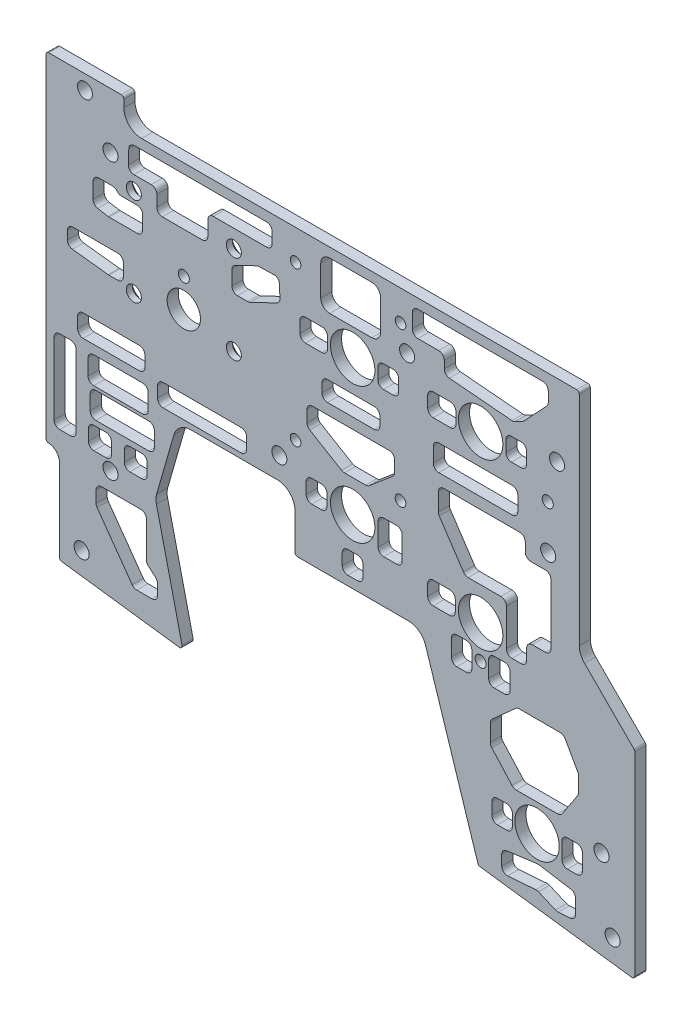
SolidWorks part; units mm, degrees
ref_plane "Front Plane" through (0, 0, 0) normal (0, 0, 1) x (1, 0, 0)
ref_plane "Top Plane" through (0, 0, 0) normal (0, 1, 0) x (1, 0, 0)
ref_plane "Right Plane" through (0, 0, 0) normal (1, 0, 0) x (0, 0, -1)
sketch "Sketch1" plane through (0, 0, 0) normal (0, 0, 1) x (1, 0, 0)
  line L16 (3.81, -91.8845) -> (3.81, -115.4033)
  line L17 (4.4725, -116.1588) -> (38.0231, -120.5758)
  line L18 (38.8645, -119.6465) -> (31.5446, -88.4134)
  line L19 (31.6093, -85.8475) -> (36.5334, -68.7608)
  line L20 (41.4148, -65.0875) -> (66.04, -65.0875)
  line L21 (71.12, -70.1675) -> (71.12, -80.518)
  line L22 (71.882, -81.28) -> (103.6122, -81.28)
  line L23 (108.4484, -84.805) -> (123.4233, -131.3792)
  line L24 (124.0493, -131.9014) -> (167.4135, -137.6104)
  line L25 (168.275, -136.8549) -> (168.275, -81.3036)
  line L26 (168.0518, -80.7647) -> (153.8879, -66.6008)
  line L27 (152.4, -63.0087) -> (152.4, -0.762)
  line L28 (151.638, 0) -> (27.305, 0)
  line L29 (22.225, 5.08) -> (22.225, 7.1755)
  line L30 (21.463, 7.9375) -> (0.762, 7.9375)
  line L31 (0, 7.1755) -> (0, -87.9495)
  line L32 (3.81, -91.8845) -> (3.81, -115.4033)
  line L33 (4.4725, -116.1588) -> (38.0231, -120.5758)
  line L34 (38.8645, -119.6465) -> (31.5446, -88.4134)
  line L35 (31.6093, -85.8475) -> (36.5334, -68.7608)
  line L36 (41.4148, -65.0875) -> (66.04, -65.0875)
  line L37 (71.12, -70.1675) -> (71.12, -80.518)
  line L38 (71.882, -81.28) -> (103.6122, -81.28)
  line L39 (108.4484, -84.805) -> (123.4233, -131.3792)
  line L40 (124.0493, -131.9014) -> (167.4135, -137.6104)
  line L41 (168.275, -136.8549) -> (168.275, -81.3036)
  line L42 (168.0518, -80.7647) -> (153.8879, -66.6008)
  line L43 (152.4, -63.0087) -> (152.4, -0.762)
  line L44 (151.638, 0) -> (27.305, 0)
  line L45 (22.225, 5.08) -> (22.225, 7.1755)
  line L46 (21.463, 7.9375) -> (0.762, 7.9375)
  line L47 (0, 7.1755) -> (0, -87.9495)
  arc A17 (3.81, -91.8845) -> (0.7374, -88.7112) centre (0.635, -91.8845) ccw
  arc A18 (3.81, -115.4033) -> (4.4725, -116.1588) centre (4.572, -115.4033) ccw
  arc A19 (38.0231, -120.5758) -> (38.8645, -119.6465) centre (38.1226, -119.8204) ccw
  arc A20 (31.6093, -85.8475) -> (31.5446, -88.4134) centre (36.4906, -87.2542) ccw
  arc A21 (41.4148, -65.0875) -> (36.5334, -68.7608) centre (41.4148, -70.1675) ccw
  arc A22 (71.12, -70.1675) -> (66.04, -65.0875) centre (66.04, -70.1675) ccw
  arc A23 (71.12, -80.518) -> (71.882, -81.28) centre (71.882, -80.518) ccw
  arc A24 (108.4484, -84.805) -> (103.6122, -81.28) centre (103.6122, -86.36) ccw
  arc A25 (123.4233, -131.3792) -> (124.0493, -131.9014) centre (124.1487, -131.1459) ccw
  arc A26 (167.4135, -137.6104) -> (168.275, -136.8549) centre (167.513, -136.8549) ccw
  arc A27 (168.275, -81.3036) -> (168.0518, -80.7647) centre (167.513, -81.3036) ccw
  arc A28 (152.4, -63.0087) -> (153.8879, -66.6008) centre (157.48, -63.0087) ccw
  arc A29 (152.4, -0.762) -> (151.638, 0) centre (151.638, -0.762) ccw
  arc A30 (22.225, 5.08) -> (27.305, 0) centre (27.305, 5.08) ccw
  arc A31 (22.225, 7.1755) -> (21.463, 7.9375) centre (21.463, 7.1755) ccw
  arc A32 (0.762, 7.9375) -> (0, 7.1755) centre (0.762, 7.1755) ccw
  arc A33 (0, -87.9495) -> (0.7374, -88.7112) centre (0.762, -87.9495) ccw
  arc A34 (3.81, -91.8845) -> (0.7374, -88.7112) centre (0.635, -91.8845) ccw
  arc A35 (3.81, -115.4033) -> (4.4725, -116.1588) centre (4.572, -115.4033) ccw
  arc A36 (38.0231, -120.5758) -> (38.8645, -119.6465) centre (38.1226, -119.8204) ccw
  arc A37 (31.6093, -85.8475) -> (31.5446, -88.4134) centre (36.4906, -87.2542) ccw
  arc A38 (41.4148, -65.0875) -> (36.5334, -68.7608) centre (41.4148, -70.1675) ccw
  arc A39 (71.12, -70.1675) -> (66.04, -65.0875) centre (66.04, -70.1675) ccw
  arc A40 (71.12, -80.518) -> (71.882, -81.28) centre (71.882, -80.518) ccw
  arc A41 (108.4484, -84.805) -> (103.6122, -81.28) centre (103.6122, -86.36) ccw
  arc A42 (123.4233, -131.3792) -> (124.0493, -131.9014) centre (124.1487, -131.1459) ccw
  arc A43 (167.4135, -137.6104) -> (168.275, -136.8549) centre (167.513, -136.8549) ccw
  arc A44 (168.275, -81.3036) -> (168.0518, -80.7647) centre (167.513, -81.3036) ccw
  arc A45 (152.4, -63.0087) -> (153.8879, -66.6008) centre (157.48, -63.0087) ccw
  arc A46 (152.4, -0.762) -> (151.638, 0) centre (151.638, -0.762) ccw
  arc A47 (22.225, 5.08) -> (27.305, 0) centre (27.305, 5.08) ccw
  arc A48 (22.225, 7.1755) -> (21.463, 7.9375) centre (21.463, 7.1755) ccw
  arc A49 (0.762, 7.9375) -> (0, 7.1755) centre (0.762, 7.1755) ccw
  arc A50 (0, -87.9495) -> (0.7374, -88.7112) centre (0.762, -87.9495) ccw
  dimension "D1" = 0
extrude "Boss-Extrude1" add sketch "Sketch1" against normal blind 3.175
hole_wizard "#6 Clearance Hole1" positions "Sketch3" profile "Sketch2" hole size "#6" standard "ANSI Inch" end condition through all
sketch "Sketch3" plane through (0, 0, -3.175) normal (0, 0, -1) x (-1, 0, 0)
  point P0 (-11.1125, 3.81)
  point P3 (-18.415, -7.9375)
  point P6 (-103.1875, -15.24)
  point P9 (-143.51, -44.45)
  point P12 (-158.75, -111.125)
  point P15 (-18.415, -86.741)
  point P18 (-66.675, -58.7375)
  point P21 (-10.16, -110.5028)
  point P25 (-146.05, -20.6375)
  point P28 (-161.925, -130.483)
sketch "Sketch2" plane through (11.1125, 3.81, -3.175) normal (1, 0, 0) x (0, 1, 0)
  line L0 (0, 0) -> (0, 3.175)
  line L1 (0, 3.175) -> (2.1526, 3.175)
  line L2 (2.1526, 3.175) -> (2.1526, 0)
  line L5 (2.1526, 0) -> (0, 0)
  line L11 (0, -6.35) -> (0, 107.95) construction
  dimension "Thru Hole Dia." = 4.3053
  dimension "Thru Hole Depth" = 3.175
sketch "Sketch4" plane through (0, 0, -3.175) normal (0, 0, -1) x (-1, 0, 0)
  circle A0 centre (-140.335, -115.57) radius 6.35
  circle A1 centre (-124.206, -71.4375) radius 6.35
  circle A2 centre (-87.63, -62.992) radius 6.35
  circle A3 centre (-87.63, -24.13) radius 6.35
  circle A4 centre (-124.206, -24.13) radius 6.35
  circle A5 centre (-124.206, -80.9625) radius 1.5875
  circle A6 centre (-39.37, -36.322) radius 4.7625
  dimension "D1" = 12.7
  dimension "D2" = 3.175
  dimension "D4" = 9.525
  dimension "D3" = 9.525
extrude "Cut-Extrude1" cut sketch "Sketch4" against normal through all
hole_wizard "CSK for #6 Flat Head Machine Screw (100)1" positions "Sketch6" profile "Sketch5" countersink size "#6" standard "ANSI Inch" end condition through all
sketch "Sketch6" plane through (0, 0, -3.175) normal (0, 0, -1) x (-1, 0, 0)
  point P0 (-53.6575, -14.097)
  point P2 (-25.0825, -14.097)
  point P4 (-25.0825, -39.497)
  point P6 (-53.6575, -39.497)
sketch "Sketch5" plane through (53.6575, -14.097, -3.175) normal (1, 0, 0) x (0, 1, 0)
  line L0 (0, 0) -> (0, 3.175)
  line L1 (0, 3.175) -> (2.1526, 3.175)
  line L2 (2.1526, 3.175) -> (2.1526, 1.4209)
  line L3 (2.1526, 1.4209) -> (3.846, 0)
  line L5 (3.846, 0) -> (0, 0)
  line L6 (-2.1526, 1.4209) -> (-3.846, 0) construction
  line L11 (0, -6.35) -> (0, 107.95) construction
  dimension "Thru Hole Dia." = 4.3053
  dimension "Thru Hole Depth" = 3.175
  dimension "Near C'Sink Dia." = 7.692
  dimension "Near C'Sink Angle" = 100
hole_wizard "#0 Clearance Hole1" positions "Sketch7" profile "Sketch8" hole size "#0" standard "ANSI Inch" end condition through all
sketch "Sketch7" plane through (0, 0, -9.525) normal (0, 0, -1) x (-1, 0, 0)
  point P0 (-39.37, -28.067)
sketch "Sketch8" plane through (39.37, -28.067, -9.525) normal (1, 0, 0) x (0, 1, 0)
  line L0 (0, 0) -> (0, 9.525)
  line L1 (0, 9.525) -> (0.9271, 9.525)
  line L2 (0.9271, 9.525) -> (0.9271, 0)
  line L3 (0.9271, 0) -> (0, 0)
  line L4 (0, -6.35) -> (0, 107.95) construction
  dimension "Thru Hole Dia." = 1.8542
  dimension "Thru Hole Depth" = 9.525
hole_wizard "1/8 (0.125) Diameter Hole1" positions "Sketch9" profile "Sketch10" hole size "1/8" standard "ANSI Inch" end condition through all
sketch "Sketch9" plane through (0, 0, 0) normal (0, 0, 1) x (1, 0, 0)
  point P0 (39.37, -28.067)
sketch "Sketch10" plane through (39.37, -28.067, 0) normal (1, 0, 0) x (0, -1, 0)
  line L0 (0, 0) -> (0, 3.175)
  line L1 (0, 3.175) -> (1.5875, 3.175)
  line L2 (1.5875, 3.175) -> (1.5875, 0)
  line L5 (1.5875, 0) -> (0, 0)
  line L11 (0, -6.35) -> (0, 107.95) construction
  dimension "Thru Hole Dia." = 3.175
  dimension "Thru Hole Depth" = 3.175
sketch "Sketch17" plane through (0, 0, 0) normal (0, 0, -1) x (-1, 0, 0)
  line L0 (-141.9544, -2.7948) -> (-106.2662, -2.7948)
  line L1 (-104.6787, -4.3823) -> (-104.6787, -8.4606)
  line L2 (-106.2662, -10.0481) -> (-112.2209, -10.0481)
  line L3 (-113.8084, -11.6356) -> (-113.8084, -13.7762)
  line L4 (-115.259, -15.3578) -> (-133.159, -16.9076)
  line L5 (-134.0131, -16.7423) -> (-136.0874, -15.6921)
  line L6 (-136.5298, -15.36) -> (-143.114, -8.3185)
  line L7 (-143.5419, -7.2342) -> (-143.5419, -4.3823)
  line L8 (-93.0669, -2.7076) -> (-81.0441, -2.7076)
  line L9 (-78.5041, -5.2476) -> (-78.5041, -13.8956)
  line L10 (-81.0441, -16.4356) -> (-93.0669, -16.4356)
  line L11 (-95.6069, -13.8956) -> (-95.6069, -5.2476)
  line L12 (-72.5612, -22.437) -> (-72.5612, -25.637)
  line L13 (-74.1487, -27.2245) -> (-78.851, -27.2245)
  line L14 (-80.4385, -25.637) -> (-80.4385, -22.437)
  line L15 (-74.1487, -20.8495) -> (-78.851, -20.8495)
  line L16 (-99.2018, -21.1963) -> (-96.4213, -21.1963)
  line L17 (-94.8338, -22.7838) -> (-94.8338, -25.9818)
  line L18 (-96.4213, -27.5693) -> (-99.2018, -27.5693)
  line L19 (-100.7893, -25.9818) -> (-100.7893, -22.7838)
  line L20 (-109.0792, -22.6549) -> (-109.0792, -25.8549)
  line L21 (-110.6667, -27.4424) -> (-115.5536, -27.4424)
  line L22 (-117.1411, -25.8549) -> (-117.1411, -22.6549)
  line L23 (-110.6667, -21.0674) -> (-115.5536, -21.0674)
  line L24 (-135.7738, -20.8814) -> (-132.9933, -20.8814)
  line L25 (-131.4058, -22.4689) -> (-131.4058, -25.667)
  line L26 (-132.9933, -27.2545) -> (-135.7738, -27.2545)
  line L27 (-137.3613, -25.667) -> (-137.3613, -22.4689)
  line L28 (-93.8189, -33.0853) -> (-80.4385, -33.0853)
  line L29 (-78.851, -34.6728) -> (-78.851, -37.1954)
  line L30 (-80.4385, -38.7829) -> (-93.8189, -38.7829)
  line L31 (-95.4064, -34.6728) -> (-95.4064, -37.1954)
  line L32 (-133.2346, -32.9063) -> (-112.2542, -32.9063)
  line L33 (-110.6667, -34.4938) -> (-110.6667, -38.6545)
  line L34 (-112.2542, -40.242) -> (-133.2346, -40.242)
  line L35 (-134.8221, -38.6545) -> (-134.8221, -34.4938)
  line L36 (-98.0498, -41.8469) -> (-76.1717, -41.8469)
  line L37 (-74.5842, -43.4344) -> (-74.5842, -46.7771)
  line L38 (-75.3596, -48.1412) -> (-84.4657, -53.5626)
  line L39 (-85.2778, -53.7861) -> (-91.3474, -53.7861)
  line L40 (-92.3756, -53.4081) -> (-99.0779, -47.711)
  line L41 (-99.6373, -46.5014) -> (-99.6373, -43.4344)
  line L42 (-135.3789, -43.4344) -> (-113.699, -43.4344)
  line L43 (-112.1115, -45.0219) -> (-112.1115, -50.0429)
  line L44 (-112.3789, -50.9245) -> (-119.3229, -61.3222)
  line L45 (-120.6431, -62.0281) -> (-129.9871, -62.0281)
  line L47 (-136.9664, -47.5212) -> (-136.9664, -45.0219)
  line L48 (-55.7285, -57.3176) -> (-33.4587, -57.3176)
  line L49 (-31.8712, -58.9051) -> (-31.8712, -62.02)
  line L50 (-33.4587, -63.6075) -> (-55.7285, -63.6075)
  line L51 (-57.316, -62.02) -> (-57.316, -58.9051)
  line L52 (-78.7021, -59.8174) -> (-75.9216, -59.8174)
  line L53 (-74.3341, -61.4049) -> (-74.3341, -64.603)
  line L54 (-75.9216, -66.1905) -> (-78.7021, -66.1905)
  line L55 (-80.2896, -64.603) -> (-80.2896, -61.4049)
  line L56 (-89.0189, -72.2548) -> (-86.2384, -72.2548)
  line L57 (-84.6509, -73.8423) -> (-84.6509, -77.0403)
  line L58 (-86.2384, -78.6278) -> (-89.0189, -78.6278)
  line L59 (-90.6064, -77.0403) -> (-90.6064, -73.8423)
  line L60 (-109.0756, -69.248) -> (-109.0756, -72.448)
  line L61 (-110.6631, -74.0355) -> (-115.3654, -74.0355)
  line L62 (-116.9529, -72.448) -> (-116.9529, -69.248)
  line L63 (-110.6631, -67.6605) -> (-115.3654, -67.6605)
  line L64 (-148.3701, -88.0766) -> (-151.9572, -94.4661)
  line L65 (-152.1698, -95.2794) -> (-152.1698, -99.4916)
  line L66 (-151.8961, -100.4052) -> (-147.5598, -106.9917)
  line L67 (-138.5539, -49.1087) -> (-142.7058, -49.1087)
  line L68 (-146.1721, -107.7395) -> (-134.3926, -107.7395)
  line L69 (-144.2933, -50.6962) -> (-144.2933, -67.8867)
  line L70 (-133.1575, -107.1893) -> (-127.3956, -100.785)
  line L71 (-126.9693, -99.6738) -> (-126.9693, -94.8668)
  line L72 (-127.5195, -93.6317) -> (-134.1629, -87.6548)
  line L73 (-135.2742, -87.2285) -> (-146.9213, -87.2285)
  line L74 (-137.3613, -71.0617) -> (-137.3613, -74.1715)
  line L75 (-135.7738, -75.759) -> (-133.1621, -75.759)
  line L76 (-131.5746, -74.1715) -> (-131.5746, -63.6156)
  line L78 (-132.6264, -79.3569) -> (-132.6264, -84.055)
  line L79 (-131.0389, -85.6425) -> (-128.0874, -85.6425)
  line L80 (-126.4999, -84.055) -> (-126.4999, -79.3653)
  line L81 (-128.0829, -77.7778) -> (-131.0344, -77.7694)
  line L82 (-121.6938, -79.414) -> (-121.6938, -84.1113)
  line L83 (-120.1063, -85.6988) -> (-117.4258, -85.6988)
  line L84 (-115.8383, -84.1113) -> (-115.8383, -79.4216)
  line L85 (-117.4212, -77.8341) -> (-120.1018, -77.8265)
  line L86 (-101.7978, -60.9375) -> (-101.7978, -67.3473)
  line L87 (-100.2103, -68.9348) -> (-96.4976, -68.9348)
  line L88 (-94.9101, -67.3473) -> (-94.9101, -60.9481)
  line L89 (-96.4931, -59.3606) -> (-100.2058, -59.35)
  line L90 (-153.2801, -113.8454) -> (-153.2801, -118.4115)
  line L91 (-151.6926, -119.999) -> (-149.0121, -119.999)
  line L92 (-147.4246, -118.4115) -> (-147.4246, -113.853)
  line L93 (-149.0076, -112.2655) -> (-151.6881, -112.2579)
  line L94 (-133.2696, -114.0603) -> (-133.2696, -117.4522)
  line L95 (-131.6821, -119.0397) -> (-129.0016, -119.0397)
  line L96 (-127.4141, -117.4522) -> (-127.4141, -114.0679)
  line L97 (-128.997, -112.4804) -> (-131.6776, -112.4728)
  line L98 (-150.0084, -124.4751) -> (-140.8902, -122.9925)
  line L99 (-140.4256, -122.9858) -> (-131.6139, -124.1607)
  line L100 (-130.2362, -125.7343) -> (-130.2362, -128.6297)
  line L101 (-131.9392, -130.213) -> (-139.9781, -129.6268)
  line L102 (-140.7126, -129.7482) -> (-145.6471, -131.838)
  line L103 (-146.3817, -131.9595) -> (-149.8691, -131.7052)
  line L104 (-151.3411, -130.1219) -> (-151.3411, -126.042)
  line L105 (-63.0404, -2.7948) -> (-25.2277, -2.7948)
  line L106 (-23.641, -4.3315) -> (-23.5105, -8.4099)
  line L107 (-25.0972, -10.0481) -> (-30.0725, -10.0481)
  line L108 (-31.66, -11.6356) -> (-31.66, -14.8481)
  line L109 (-33.2475, -16.4356) -> (-44.6401, -16.4356)
  line L110 (-46.2276, -14.8481) -> (-46.2276, -10.6224)
  line L111 (-47.8151, -9.0349) -> (-63.0404, -9.0349)
  line L112 (-64.6279, -7.4474) -> (-64.6279, -4.3823)
  line L113 (-14.7591, -23.5708) -> (-17.7234, -24.0903)
  line L114 (-17.9974, -24.1142) -> (-26.0381, -24.1142)
  line L115 (-27.6256, -22.5267) -> (-27.6256, -18.7366)
  line L116 (-26.0381, -17.1491) -> (-21.5632, -17.1491)
  line L117 (-20.4504, -16.6939) -> (-20.1204, -16.3695)
  line L118 (-19.0076, -15.9142) -> (-15.0331, -15.9142)
  line L119 (-13.4456, -17.5017) -> (-13.4456, -22.0071)
  line L120 (-7.6875, -31.7843) -> (-20.4927, -31.7843)
  line L121 (-22.0802, -33.3718) -> (-22.0802, -36.9105)
  line L122 (-20.4927, -38.498) -> (-17.9504, -38.498)
  line L123 (-17.7686, -38.4875) -> (-7.5058, -37.3048)
  line L124 (-6.1, -35.7277) -> (-6.1, -33.3718)
  line L125 (-54.0177, -18.0353) -> (-60.157, -15.0963)
  line L126 (-60.7931, -14.9415) -> (-65.0805, -14.8081)
  line L127 (-66.7166, -16.3454) -> (-66.8282, -19.9294)
  line L128 (-65.9269, -21.4107) -> (-58.3022, -25.0607)
  line L129 (-57.6167, -25.2163) -> (-54.7032, -25.2163)
  line L130 (-53.1157, -23.6288) -> (-53.1157, -19.4672)
  line L131 (-24.6224, -111.8142) -> (-14.5986, -97.7476)
  line L132 (-14.304, -96.8263) -> (-14.304, -93.5113)
  line L133 (-2.2976, -61.6269) -> (-2.2976, -82.1859)
  line L134 (-3.8851, -83.7734) -> (-6.9926, -83.7734)
  line L135 (-8.5801, -82.1859) -> (-8.5801, -61.6269)
  line L136 (-6.9926, -60.0394) -> (-3.8851, -60.0394)
  line L137 (-15.8915, -91.9238) -> (-27.0858, -91.9238)
  line L138 (-28.6733, -93.5113) -> (-28.6733, -103.656)
  line L139 (-29.2117, -104.8474) -> (-31.3328, -106.7152)
  line L140 (-31.8712, -107.9067) -> (-31.8712, -110.8929)
  line L141 (-30.2837, -112.4804) -> (-25.9153, -112.4804)
  line L142 (-26.655, -51.5392) -> (-10.6039, -51.5392)
  line L143 (-9.0164, -53.1267) -> (-9.0164, -56.2416)
  line L144 (-10.6039, -57.8291) -> (-26.655, -57.8291)
  line L145 (-28.2425, -56.2416) -> (-28.2425, -53.1267)
  line L146 (-27.6052, -60.385) -> (-13.5866, -60.385)
  line L147 (-11.9991, -61.9725) -> (-11.9991, -66.4544)
  line L148 (-13.5866, -68.0419) -> (-27.6052, -68.0419)
  line L149 (-29.1927, -66.4544) -> (-29.1927, -61.9725)
  line L150 (-29.347, -68.9032) -> (-14.2014, -68.9032)
  line L151 (-12.6139, -70.4907) -> (-12.6139, -74.7412)
  line L152 (-14.2014, -76.3287) -> (-29.347, -76.3287)
  line L153 (-30.9345, -74.7412) -> (-30.9345, -70.4907)
  line L154 (-27.3287, -77.9076) -> (-23.9481, -77.9076)
  line L155 (-22.3606, -79.4951) -> (-22.3606, -82.61)
  line L156 (-23.9481, -84.1975) -> (-27.3287, -84.1975)
  line L157 (-28.9162, -82.61) -> (-28.9162, -79.4951)
  line L158 (-17.1192, -77.821) -> (-13.667, -77.821)
  line L159 (-12.0795, -79.4085) -> (-12.0795, -82.5234)
  line L160 (-13.667, -84.1109) -> (-17.1192, -84.1109)
  line L161 (-18.7067, -82.5234) -> (-18.7067, -79.4085)
  line L162 (-142.7058, -69.4742) -> (-138.9488, -69.4742)
  arc A0 (-106.2662, -2.7948) -> (-104.6787, -4.3823) centre (-106.2662, -4.3823) cw
  arc A1 (-104.6787, -8.4606) -> (-106.2662, -10.0481) centre (-106.2662, -8.4606) cw
  arc A2 (-112.2209, -10.0481) -> (-113.8084, -11.6356) centre (-112.2209, -11.6356) ccw
  arc A3 (-113.8084, -13.7762) -> (-115.259, -15.3578) centre (-115.3959, -13.7762) cw
  arc A4 (-133.159, -16.9076) -> (-134.0131, -16.7423) centre (-133.296, -15.326) cw
  arc A5 (-136.0874, -15.6921) -> (-136.5298, -15.36) centre (-135.3703, -14.2758) cw
  arc A6 (-143.114, -8.3185) -> (-143.5419, -7.2342) centre (-141.9544, -7.2342) cw
  arc A7 (-141.9544, -2.7948) -> (-143.5419, -4.3823) centre (-141.9544, -4.3823) ccw
  arc A8 (-81.0441, -2.7076) -> (-78.5041, -5.2476) centre (-81.0441, -5.2476) cw
  arc A9 (-78.5041, -13.8956) -> (-81.0441, -16.4356) centre (-81.0441, -13.8956) cw
  arc A10 (-93.0669, -16.4356) -> (-95.6069, -13.8956) centre (-93.0669, -13.8956) cw
  arc A11 (-93.0669, -2.7076) -> (-95.6069, -5.2476) centre (-93.0669, -5.2476) ccw
  arc A12 (-72.5612, -22.437) -> (-74.1487, -20.8495) centre (-74.1487, -22.437) ccw
  arc A13 (-72.5612, -25.637) -> (-74.1487, -27.2245) centre (-74.1487, -25.637) cw
  arc A14 (-78.851, -27.2245) -> (-80.4385, -25.637) centre (-78.851, -25.637) cw
  arc A15 (-80.4385, -22.437) -> (-78.851, -20.8495) centre (-78.851, -22.437) cw
  arc A16 (-96.4213, -21.1963) -> (-94.8338, -22.7838) centre (-96.4213, -22.7838) cw
  arc A17 (-94.8338, -25.9818) -> (-96.4213, -27.5693) centre (-96.4213, -25.9818) cw
  arc A18 (-99.2018, -27.5693) -> (-100.7893, -25.9818) centre (-99.2018, -25.9818) cw
  arc A19 (-99.2018, -21.1963) -> (-100.7893, -22.7838) centre (-99.2018, -22.7838) ccw
  arc A20 (-109.0792, -22.6549) -> (-110.6667, -21.0674) centre (-110.6667, -22.6549) ccw
  arc A21 (-109.0792, -25.8549) -> (-110.6667, -27.4424) centre (-110.6667, -25.8549) cw
  arc A22 (-115.5536, -27.4424) -> (-117.1411, -25.8549) centre (-115.5536, -25.8549) cw
  arc A23 (-117.1411, -22.6549) -> (-115.5536, -21.0674) centre (-115.5536, -22.6549) cw
  arc A24 (-132.9933, -20.8814) -> (-131.4058, -22.4689) centre (-132.9933, -22.4689) cw
  arc A25 (-131.4058, -25.667) -> (-132.9933, -27.2545) centre (-132.9933, -25.667) cw
  arc A26 (-135.7738, -27.2545) -> (-137.3613, -25.667) centre (-135.7738, -25.667) cw
  arc A27 (-135.7738, -20.8814) -> (-137.3613, -22.4689) centre (-135.7738, -22.4689) ccw
  arc A28 (-80.4385, -33.0853) -> (-78.851, -34.6728) centre (-80.4385, -34.6728) cw
  arc A29 (-78.851, -37.1954) -> (-80.4385, -38.7829) centre (-80.4385, -37.1954) cw
  arc A30 (-93.8189, -38.7829) -> (-95.4064, -37.1954) centre (-93.8189, -37.1954) cw
  arc A31 (-93.8189, -33.0853) -> (-95.4064, -34.6728) centre (-93.8189, -34.6728) ccw
  arc A32 (-112.2542, -32.9063) -> (-110.6667, -34.4938) centre (-112.2542, -34.4938) cw
  arc A33 (-110.6667, -38.6545) -> (-112.2542, -40.242) centre (-112.2542, -38.6545) cw
  arc A34 (-133.2346, -40.242) -> (-134.8221, -38.6545) centre (-133.2346, -38.6545) cw
  arc A35 (-133.2346, -32.9063) -> (-134.8221, -34.4938) centre (-133.2346, -34.4938) ccw
  arc A36 (-91.3474, -53.7861) -> (-92.3756, -53.4081) centre (-91.3474, -52.1986) cw
  arc A37 (-84.4657, -53.5626) -> (-85.2778, -53.7861) centre (-85.2778, -52.1986) cw
  arc A38 (-74.5842, -46.7771) -> (-75.3596, -48.1412) centre (-76.1717, -46.7771) cw
  arc A39 (-76.1717, -41.8469) -> (-74.5842, -43.4344) centre (-76.1717, -43.4344) cw
  arc A40 (-98.0498, -41.8469) -> (-99.6373, -43.4344) centre (-98.0498, -43.4344) ccw
  arc A41 (-99.0779, -47.711) -> (-99.6373, -46.5014) centre (-98.0498, -46.5014) cw
  arc A42 (-113.699, -43.4344) -> (-112.1115, -45.0219) centre (-113.699, -45.0219) cw
  arc A43 (-112.1115, -50.0429) -> (-112.3789, -50.9245) centre (-113.699, -50.0429) cw
  arc A44 (-119.3229, -61.3222) -> (-120.6431, -62.0281) centre (-120.6431, -60.4406) cw
  arc A47 (-135.3789, -43.4344) -> (-136.9664, -45.0219) centre (-135.3789, -45.0219) ccw
  arc A48 (-33.4587, -57.3176) -> (-31.8712, -58.9051) centre (-33.4587, -58.9051) cw
  arc A49 (-31.8712, -62.02) -> (-33.4587, -63.6075) centre (-33.4587, -62.02) cw
  arc A50 (-55.7285, -63.6075) -> (-57.316, -62.02) centre (-55.7285, -62.02) cw
  arc A51 (-55.7285, -57.3176) -> (-57.316, -58.9051) centre (-55.7285, -58.9051) ccw
  arc A52 (-75.9216, -59.8174) -> (-74.3341, -61.4049) centre (-75.9216, -61.4049) cw
  arc A53 (-74.3341, -64.603) -> (-75.9216, -66.1905) centre (-75.9216, -64.603) cw
  arc A54 (-78.7021, -66.1905) -> (-80.2896, -64.603) centre (-78.7021, -64.603) cw
  arc A55 (-78.7021, -59.8174) -> (-80.2896, -61.4049) centre (-78.7021, -61.4049) ccw
  arc A56 (-86.2384, -72.2548) -> (-84.6509, -73.8423) centre (-86.2384, -73.8423) cw
  arc A57 (-84.6509, -77.0403) -> (-86.2384, -78.6278) centre (-86.2384, -77.0403) cw
  arc A58 (-89.0189, -78.6278) -> (-90.6064, -77.0403) centre (-89.0189, -77.0403) cw
  arc A59 (-89.0189, -72.2548) -> (-90.6064, -73.8423) centre (-89.0189, -73.8423) ccw
  arc A60 (-109.0756, -69.248) -> (-110.6631, -67.6605) centre (-110.6631, -69.248) ccw
  arc A61 (-109.0756, -72.448) -> (-110.6631, -74.0355) centre (-110.6631, -72.448) cw
  arc A62 (-115.3654, -74.0355) -> (-116.9529, -72.448) centre (-115.3654, -72.448) cw
  arc A63 (-116.9529, -69.248) -> (-115.3654, -67.6605) centre (-115.3654, -69.248) cw
  arc A64 (-134.1629, -87.6548) -> (-135.2742, -87.2285) centre (-135.2742, -88.8899) ccw
  arc A65 (-126.9693, -94.8668) -> (-127.5195, -93.6317) centre (-128.6308, -94.8668) ccw
  arc A66 (-127.3956, -100.785) -> (-126.9693, -99.6738) centre (-128.6308, -99.6738) ccw
  arc A67 (-134.3926, -107.7395) -> (-133.1575, -107.1893) centre (-134.3926, -106.0781) ccw
  arc A68 (-147.5598, -106.9917) -> (-146.1721, -107.7395) centre (-146.1721, -106.0781) ccw
  arc A69 (-152.1698, -99.4916) -> (-151.8961, -100.4052) centre (-150.5084, -99.4916) ccw
  arc A70 (-151.9572, -94.4661) -> (-152.1698, -95.2794) centre (-150.5084, -95.2794) ccw
  arc A71 (-148.3701, -88.0766) -> (-146.9213, -87.2285) centre (-146.9213, -88.8899) cw
  arc A74 (-133.1621, -75.759) -> (-131.5746, -74.1715) centre (-133.1621, -74.1715) ccw
  arc A75 (-137.3613, -74.1715) -> (-135.7738, -75.759) centre (-135.7738, -74.1715) ccw
  arc A76 (-132.6264, -79.3569) -> (-131.0344, -77.7694) centre (-131.0389, -79.3569) cw
  arc A77 (-126.4999, -79.3653) -> (-128.0829, -77.7778) centre (-128.0874, -79.3653) ccw
  arc A78 (-128.0874, -85.6425) -> (-126.4999, -84.055) centre (-128.0874, -84.055) ccw
  arc A79 (-132.6264, -84.055) -> (-131.0389, -85.6425) centre (-131.0389, -84.055) ccw
  arc A80 (-121.6938, -79.414) -> (-120.1018, -77.8265) centre (-120.1063, -79.414) cw
  arc A81 (-115.8383, -79.4216) -> (-117.4212, -77.8341) centre (-117.4258, -79.4216) ccw
  arc A82 (-117.4258, -85.6988) -> (-115.8383, -84.1113) centre (-117.4258, -84.1113) ccw
  arc A83 (-121.6938, -84.1113) -> (-120.1063, -85.6988) centre (-120.1063, -84.1113) ccw
  arc A84 (-101.7978, -60.9375) -> (-100.2058, -59.35) centre (-100.2103, -60.9375) cw
  arc A85 (-94.9101, -60.9481) -> (-96.4931, -59.3606) centre (-96.4976, -60.9481) ccw
  arc A86 (-96.4976, -68.9348) -> (-94.9101, -67.3473) centre (-96.4976, -67.3473) ccw
  arc A87 (-101.7978, -67.3473) -> (-100.2103, -68.9348) centre (-100.2103, -67.3473) ccw
  arc A88 (-153.2801, -113.8454) -> (-151.6881, -112.2579) centre (-151.6926, -113.8454) cw
  arc A89 (-147.4246, -113.853) -> (-149.0076, -112.2655) centre (-149.0121, -113.853) ccw
  arc A90 (-149.0121, -119.999) -> (-147.4246, -118.4115) centre (-149.0121, -118.4115) ccw
  arc A91 (-153.2801, -118.4115) -> (-151.6926, -119.999) centre (-151.6926, -118.4115) ccw
  arc A92 (-133.2696, -114.0603) -> (-131.6776, -112.4728) centre (-131.6821, -114.0603) cw
  arc A93 (-127.4141, -114.0679) -> (-128.997, -112.4804) centre (-129.0016, -114.0679) ccw
  arc A94 (-129.0016, -119.0397) -> (-127.4141, -117.4522) centre (-129.0016, -117.4522) ccw
  arc A95 (-133.2696, -117.4522) -> (-131.6821, -119.0397) centre (-131.6821, -117.4522) ccw
  arc A96 (-140.8902, -122.9925) -> (-140.4256, -122.9858) centre (-140.6354, -124.5594) cw
  arc A97 (-131.6139, -124.1607) -> (-130.2362, -125.7343) centre (-131.8237, -125.7343) cw
  arc A98 (-130.2362, -128.6297) -> (-131.9392, -130.213) centre (-131.8237, -128.6297) cw
  arc A99 (-139.9781, -129.6268) -> (-140.7126, -129.7482) centre (-140.0935, -131.2101) ccw
  arc A100 (-145.6471, -131.838) -> (-146.3817, -131.9595) centre (-146.2662, -130.3762) cw
  arc A101 (-149.8691, -131.7052) -> (-151.3411, -130.1219) centre (-149.7536, -130.1219) cw
  arc A102 (-150.0084, -124.4751) -> (-151.3411, -126.042) centre (-149.7536, -126.042) ccw
  arc A103 (-63.0404, -2.7948) -> (-64.6279, -4.3823) centre (-63.0404, -4.3823) ccw
  arc A104 (-25.2277, -2.7948) -> (-23.641, -4.3315) centre (-25.2277, -4.3823) cw
  arc A105 (-23.5105, -8.4099) -> (-25.0972, -10.0481) centre (-25.0972, -8.4606) cw
  arc A106 (-30.0725, -10.0481) -> (-31.66, -11.6356) centre (-30.0725, -11.6356) ccw
  arc A107 (-31.66, -14.8481) -> (-33.2475, -16.4356) centre (-33.2475, -14.8481) cw
  arc A108 (-44.6401, -16.4356) -> (-46.2276, -14.8481) centre (-44.6401, -14.8481) cw
  arc A109 (-46.2276, -10.6224) -> (-47.8151, -9.0349) centre (-47.8151, -10.6224) ccw
  arc A110 (-63.0404, -9.0349) -> (-64.6279, -7.4474) centre (-63.0404, -7.4474) cw
  arc A111 (-23.9481, -77.9076) -> (-22.3606, -79.4951) centre (-23.9481, -79.4951) cw
  arc A112 (-21.5632, -17.1491) -> (-20.4504, -16.6939) centre (-21.5632, -15.5616) ccw
  arc A113 (-20.1204, -16.3695) -> (-19.0076, -15.9142) centre (-19.0076, -17.5017) cw
  arc A114 (-15.0331, -15.9142) -> (-13.4456, -17.5017) centre (-15.0331, -17.5017) cw
  arc A115 (-14.7591, -23.5708) -> (-13.4456, -22.0071) centre (-15.0331, -22.0071) ccw
  arc A116 (-17.7234, -24.0903) -> (-17.9974, -24.1142) centre (-17.9974, -22.5267) cw
  arc A117 (-26.0381, -24.1142) -> (-27.6256, -22.5267) centre (-26.0381, -22.5267) cw
  arc A118 (-27.6256, -18.7366) -> (-26.0381, -17.1491) centre (-26.0381, -18.7366) cw
  arc A119 (-20.4927, -31.7843) -> (-22.0802, -33.3718) centre (-20.4927, -33.3718) ccw
  arc A120 (-22.0802, -36.9105) -> (-20.4927, -38.498) centre (-20.4927, -36.9105) ccw
  arc A121 (-17.9504, -38.498) -> (-17.7686, -38.4875) centre (-17.9504, -36.9105) ccw
  arc A122 (-7.5058, -37.3048) -> (-6.1, -35.7277) centre (-7.6875, -35.7277) ccw
  arc A123 (-7.6875, -31.7843) -> (-6.1, -33.3718) centre (-7.6875, -33.3718) cw
  arc A124 (-58.3022, -25.0607) -> (-57.6167, -25.2163) centre (-57.6167, -23.6288) ccw
  arc A125 (-54.7032, -25.2163) -> (-53.1157, -23.6288) centre (-54.7032, -23.6288) ccw
  arc A126 (-54.0177, -18.0353) -> (-53.1157, -19.4672) centre (-54.7032, -19.4672) cw
  arc A127 (-60.157, -15.0963) -> (-60.7931, -14.9415) centre (-60.8425, -16.5282) ccw
  arc A128 (-65.0805, -14.8081) -> (-66.7166, -16.3454) centre (-65.1299, -16.3948) ccw
  arc A129 (-66.8282, -19.9294) -> (-65.9269, -21.4107) centre (-65.2414, -19.9788) ccw
  arc A130 (-6.9926, -83.7734) -> (-8.5801, -82.1859) centre (-6.9926, -82.1859) cw
  arc A131 (-2.2976, -82.1859) -> (-3.8851, -83.7734) centre (-3.8851, -82.1859) cw
  arc A132 (-3.8851, -60.0394) -> (-2.2976, -61.6269) centre (-3.8851, -61.6269) cw
  arc A133 (-8.5801, -61.6269) -> (-6.9926, -60.0394) centre (-6.9926, -61.6269) cw
  arc A134 (-14.304, -93.5113) -> (-15.8915, -91.9238) centre (-15.8915, -93.5113) ccw
  arc A135 (-14.5986, -97.7476) -> (-14.304, -96.8263) centre (-15.8915, -96.8263) ccw
  arc A136 (-24.6224, -111.8142) -> (-25.9153, -112.4804) centre (-25.9153, -110.8929) cw
  arc A137 (-31.8712, -110.8929) -> (-30.2837, -112.4804) centre (-30.2837, -110.8929) ccw
  arc A138 (-31.3328, -106.7152) -> (-31.8712, -107.9067) centre (-30.2837, -107.9067) ccw
  arc A139 (-28.6733, -103.656) -> (-29.2117, -104.8474) centre (-30.2608, -103.656) cw
  arc A140 (-27.0858, -91.9238) -> (-28.6733, -93.5113) centre (-27.0858, -93.5113) ccw
  arc A141 (-10.6039, -51.5392) -> (-9.0164, -53.1267) centre (-10.6039, -53.1267) cw
  arc A142 (-9.0164, -56.2416) -> (-10.6039, -57.8291) centre (-10.6039, -56.2416) cw
  arc A143 (-26.655, -57.8291) -> (-28.2425, -56.2416) centre (-26.655, -56.2416) cw
  arc A144 (-26.655, -51.5392) -> (-28.2425, -53.1267) centre (-26.655, -53.1267) ccw
  arc A145 (-13.5866, -60.385) -> (-11.9991, -61.9725) centre (-13.5866, -61.9725) cw
  arc A146 (-11.9991, -66.4544) -> (-13.5866, -68.0419) centre (-13.5866, -66.4544) cw
  arc A147 (-27.6052, -68.0419) -> (-29.1927, -66.4544) centre (-27.6052, -66.4544) cw
  arc A148 (-27.6052, -60.385) -> (-29.1927, -61.9725) centre (-27.6052, -61.9725) ccw
  arc A149 (-14.2014, -68.9032) -> (-12.6139, -70.4907) centre (-14.2014, -70.4907) cw
  arc A150 (-12.6139, -74.7412) -> (-14.2014, -76.3287) centre (-14.2014, -74.7412) cw
  arc A151 (-29.347, -76.3287) -> (-30.9345, -74.7412) centre (-29.347, -74.7412) cw
  arc A152 (-29.347, -68.9032) -> (-30.9345, -70.4907) centre (-29.347, -70.4907) ccw
  arc A153 (-22.3606, -82.61) -> (-23.9481, -84.1975) centre (-23.9481, -82.61) cw
  arc A154 (-27.3287, -84.1975) -> (-28.9162, -82.61) centre (-27.3287, -82.61) cw
  arc A155 (-27.3287, -77.9076) -> (-28.9162, -79.4951) centre (-27.3287, -79.4951) ccw
  arc A156 (-13.667, -77.821) -> (-12.0795, -79.4085) centre (-13.667, -79.4085) cw
  arc A157 (-12.0795, -82.5234) -> (-13.667, -84.1109) centre (-13.667, -82.5234) cw
  arc A158 (-17.1192, -84.1109) -> (-18.7067, -82.5234) centre (-17.1192, -82.5234) cw
  arc A159 (-17.1192, -77.821) -> (-18.7067, -79.4085) centre (-17.1192, -79.4085) ccw
  circle A160 centre (-143.3865, -31.863) radius 1.5875
  arc A161 (-136.9664, -47.5212) -> (-138.5539, -49.1087) centre (-138.5539, -47.5212) cw
  arc A162 (-142.7058, -49.1087) -> (-144.2933, -50.6962) centre (-142.7058, -50.6962) ccw
  arc A163 (-144.2933, -67.8867) -> (-142.7058, -69.4742) centre (-142.7058, -67.8867) ccw
  arc A164 (-137.3613, -71.0617) -> (-138.9488, -69.4742) centre (-138.9488, -71.0617) ccw
  arc A165 (-131.5746, -63.6156) -> (-129.9871, -62.0281) centre (-129.9871, -63.6156) cw
  point P212 (-133.6525, -107.7395)
  point P215 (-147.0675, -107.7395)
  dimension "D1" = 1.5875
  dimension "D2" = 2.54
  dimension "D3" = 1.5875
  dimension "D4" = 1.5875
  dimension "D5" = 1.5875
  dimension "D6" = 1.5875
  dimension "D7" = 1.5875
  dimension "D8" = 1.5875
  dimension "D9" = 1.5875
  dimension "D10" = 1.5875
  dimension "D11" = 1.6614
  dimension "D12" = 1.5875
  dimension "D13" = 1.5875
  dimension "D14" = 1.5875
  dimension "D15" = 1.5875
  dimension "D16" = 1.5875
  dimension "D17" = 1.5875
  dimension "D18" = 1.5875
  dimension "D19" = 1.5875
  dimension "D20" = 3.175
extrude "Backlighting Holes" cut sketch "Sketch17" along normal through all
sketch "Sketch20" plane through (0, 0, 0) normal (0, 0, 1) x (1, 0, 0)
  line L2 (71.3117, -8.663) -> (101.3117, -8.663) construction
  line L3 (101.3117, -8.663) -> (101.3117, -52.663) construction
  line L4 (101.3117, -52.663) -> (71.3117, -52.663) construction
  line L5 (71.3117, -52.663) -> (71.3117, -8.663) construction
  line L6 (71.3117, -8.663) -> (71.3117, 0) construction
  line L8 (152.4, -8.663) -> (101.3117, -8.663) construction
  line L9 (152.4, -63.0087) -> (152.4, -0.762) construction
  circle A0 centre (101.3117, -8.663) radius 1.52
  circle A1 centre (71.3117, -8.663) radius 1.52
  circle A2 centre (101.3117, -52.663) radius 1.52
  circle A3 centre (71.3117, -52.663) radius 1.52
  dimension "D2" = 51.0883
  dimension "D3" = 30
  dimension "D4" = 44
extrude "Switch PCB Mounting Holes" cut sketch "Sketch20" against normal through all
